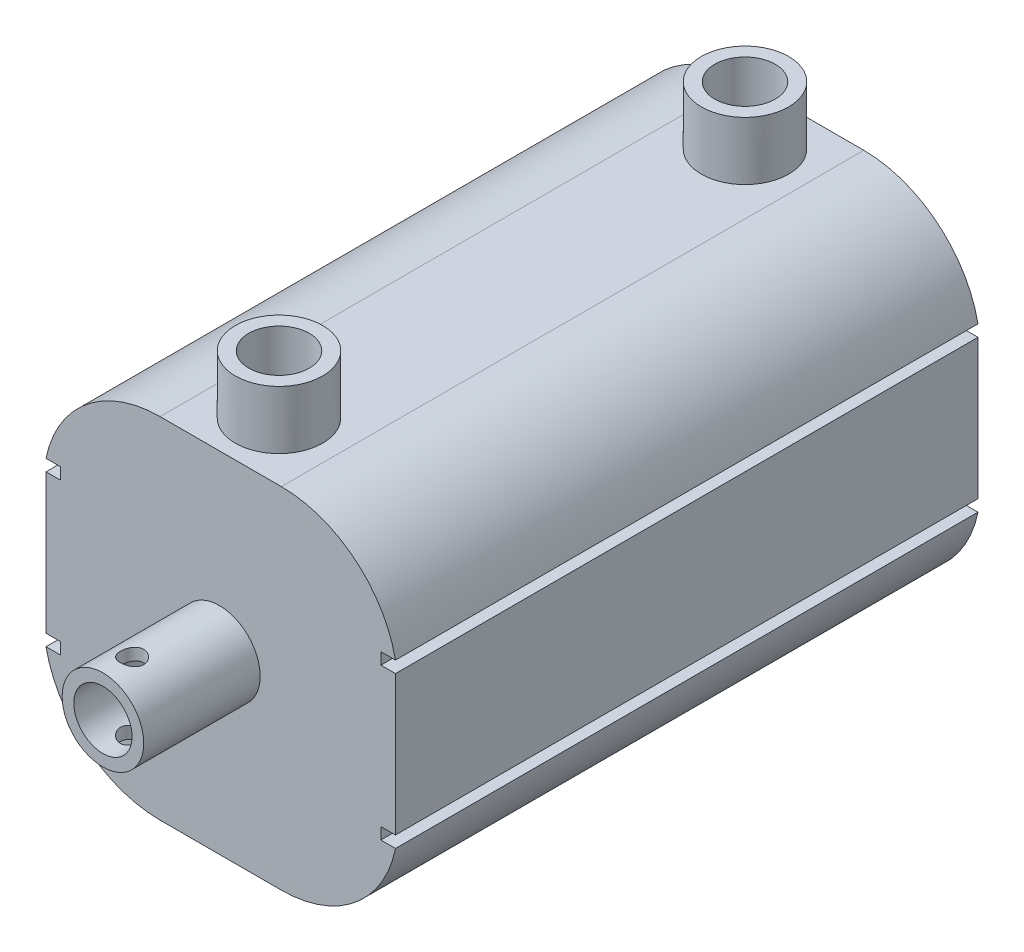
SolidWorks part; units mm, degrees
ref_plane "Front Plane" through (0, 0, 0) normal (0, 0, 1) x (1, 0, 0)
ref_plane "Top Plane" through (0, 0, 0) normal (0, 1, 0) x (1, 0, 0)
ref_plane "Right Plane" through (0, 0, 0) normal (1, 0, 0) x (0, 0, -1)
sketch "Sketch1" plane through (0, 0, 0) normal (1, 0, 0) x (0, 0, -1)
  line L1 (-25, -15) -> (25, -15)
  line L2 (-25, -15) -> (-25, 15)
  line L3 (-25, 15) -> (25, 15)
  line L4 (25, -15) -> (25, 15)
  line L5 (-25, -15) -> (25, 15) construction
  line L6 (-25, 15) -> (25, -15) construction
  point P0 (0, 0)
  dimension "D1" = 50
  dimension "D2" = 30
extrude "Boss-Extrude1" add sketch "Sketch1" along normal blind 30
sketch "Sketch3" plane through (0, 0, -25) normal (0, 0, -1) x (-1, 0, 0)
  line L0 (-30, -15) -> (-30, 15) construction
  circle A0 centre (-15, 0) radius 5
  point P2 (-30, 0)
  dimension "D2" = 10
  dimension "D1" = 15
extrude "Cut-Extrude1" cut sketch "Sketch3" against normal blind 40
sketch "Sketch4" plane through (0, 0, -25) normal (0, 0, -1) x (-1, 0, 0)
  line L0 (-30, -15) -> (-30, 15) construction
  line L1 (-30, 7) -> (-28.745, 7)
  line L2 (-30, 7) -> (-30, 6)
  line L3 (-30, 6) -> (-28.745, 6)
  line L4 (-28.745, 7) -> (-28.745, 6)
  line L5 (-30, 15) -> (0, 15) construction
  line L6 (-30, -6) -> (-28.745, -6)
  line L7 (-30, -6) -> (-30, -7)
  line L8 (-30, -7) -> (-28.745, -7)
  line L9 (-28.745, -6) -> (-28.745, -7)
  line L10 (-30, -15) -> (0, -15) construction
  line L11 (-15, 15) -> (-15, -15) construction
  line L12 (-1.255, -6) -> (-1.255, -7)
  line L13 (0, -7) -> (-1.255, -7)
  line L14 (0, -6) -> (-1.255, -6)
  line L15 (0, -6) -> (0, -7)
  line L16 (0, 7) -> (0, 6)
  line L17 (0, 6) -> (-1.255, 6)
  line L18 (-1.255, 7) -> (-1.255, 6)
  line L19 (0, 7) -> (-1.255, 7)
  dimension "D1" = 1
  dimension "D2" = 1
  dimension "D3" = 8
  dimension "D4" = 8
extrude "Cut-Extrude2" cut sketch "Sketch4" against normal through all
sketch "Sketch5" plane through (0, 15, 0) normal (0, 1, 0) x (1, 0, 0)
  circle A0 centre (15, 20) radius 2.5
  circle A1 centre (15, -20) radius 2.5971
  dimension "D1" = 40
extrude "Cut-Extrude3" cut sketch "Sketch5" against normal blind 18
sketch "Sketch6" plane through (0, 15, 0) normal (0, 1, 0) x (1, 0, 0)
  line L0 (0, 25) -> (0, -25) construction
  line L1 (30, 25) -> (0, 25) construction
  circle A0 centre (15, -20) radius 3.75
  circle A1 centre (15, 20) radius 3.75
  circle A2 centre (15, -20) radius 2.5971
  circle A3 centre (15, 20) radius 2.5971
  dimension "D1" = 7.5
  dimension "D2" = 15
  dimension "D3" = 5
extrude "Boss-Extrude2" add sketch "Sketch6" along normal blind 5
sketch "Sketch7" plane through (0, 0, 15) normal (0, 0, -1) x (-1, 0, 0)
  circle A0 centre (-15, 0) radius 2.5
extrude "Cut-Extrude4" cut sketch "Sketch7" against normal blind 5
sketch "Sketch8" plane through (0, 0, 25) normal (0, 0, 1) x (1, 0, 0)
  circle A0 centre (14.8856, 0) radius 2.5
  circle A1 centre (14.8856, 0) radius 3.5
  dimension "D1" = 1
  dimension "D2" = 5
extrude "Boss-Extrude3" add sketch "Sketch8" along normal blind 10
sketch "Sketch9" plane through (0, 15, 0) normal (0, 1, 0) x (1, 0, 0)
  line L0 (11.3856, -35) -> (18.3856, -35) construction
  line L1 (11.3856, -25) -> (11.3856, -35) construction
  circle A0 centre (14.8856, -32.5) radius 1
  dimension "D1" = 2.5
  dimension "D2" = 3.5
extrude "Cut-Extrude5" cut sketch "Sketch9" against normal through all
fillet "Fillet1" radius 10 4 edges at (30, -15, 0) (0, -15, 0) (0, 15, 0) (30, 15, 0)
